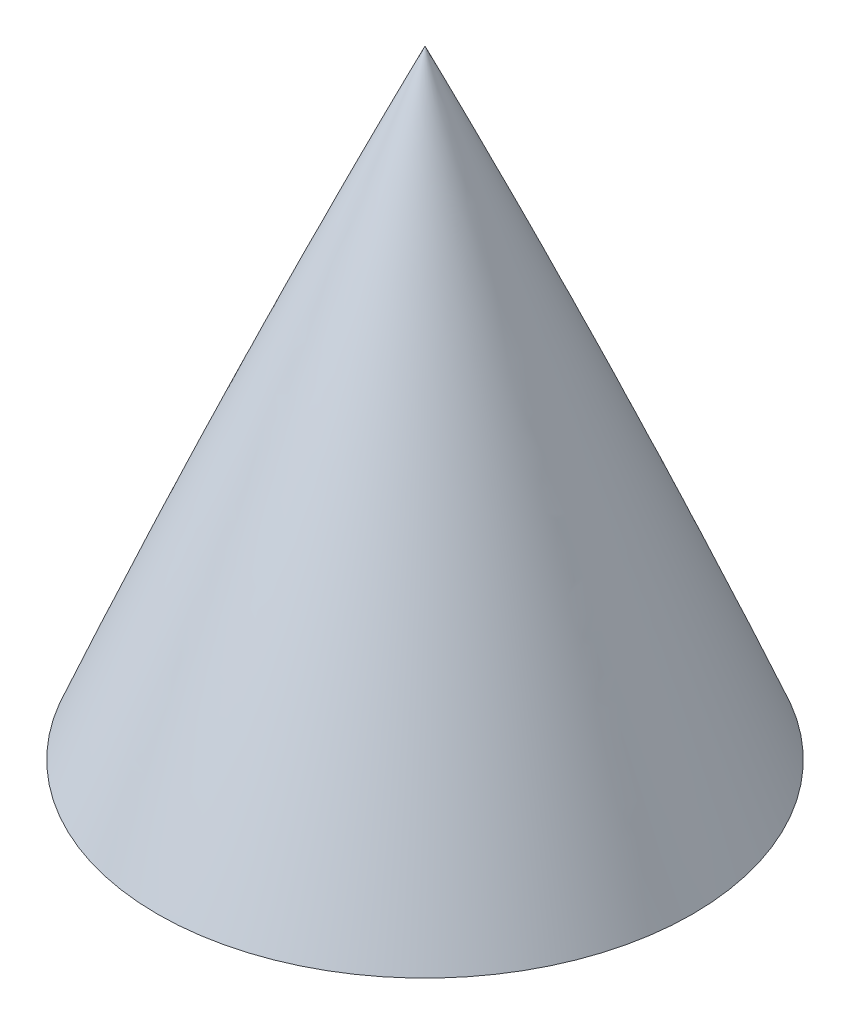
SolidWorks part; units mm, degrees
material "PVB"
ref_plane "Front Plane" through (0, 0, 0) normal (0, 0, 1) x (1, 0, 0)
ref_plane "Top Plane" through (0, 0, 0) normal (0, 1, 0) x (1, 0, 0)
ref_plane "Right Plane" through (0, 0, 0) normal (1, 0, 0) x (0, 0, -1)
sketch "Sketch2" plane through (0, 0, 0) normal (0, 0, 1) x (1, 0, 0)
  line L0 (0, 0) -> (0, 381) construction
  line L1 (-98.425, 0) -> (-90.551, 0)
  line L2 (0, 381) -> (0, 375.92)
  line L3 (0, 375.92) -> (0, 0)
  line L4 (0, 0) -> (-90.551, 0)
  arc A0 (0, 381) -> (-98.425, 0) centre (992.1135, -78.5092) ccw
  dimension "D1" = 381
  dimension "D2" = 5.08
  dimension "D3" = 98.425
  dimension "D4" = 7.874
revolve "Revolve1" add sketch "Sketch2" angle 360 about L2
sketch "Sketch3" plane through (0, 0, 0) normal (0, -1, 0) x (1, 0, 0)
  circle A0 centre (0, 0) radius 88.9
  circle A1 centre (0, 0) radius 86.995
  dimension "D1" = 177.8
extrude "Boss-Extrude1" [suppressed] add sketch "Sketch3" along normal blind 35.56
sketch "Sketch7" plane through (0, 0, 0) normal (0, -1, 0) x (1, 0, 0)
  circle A0 centre (-188.315, 83.0177) radius 421.4958
extrude "Cut-Extrude2" cut sketch "Sketch7" against normal blind 330.2
sketch "Sketch8" plane through (0, 330.2, 0) normal (0, -1, 0) x (-1, 0, 0)
  circle A0 centre (0, 0) radius 3.175
  dimension "D1" = 6.35
extrude "Cut-Extrude3" cut sketch "Sketch8" against normal blind 12.7
